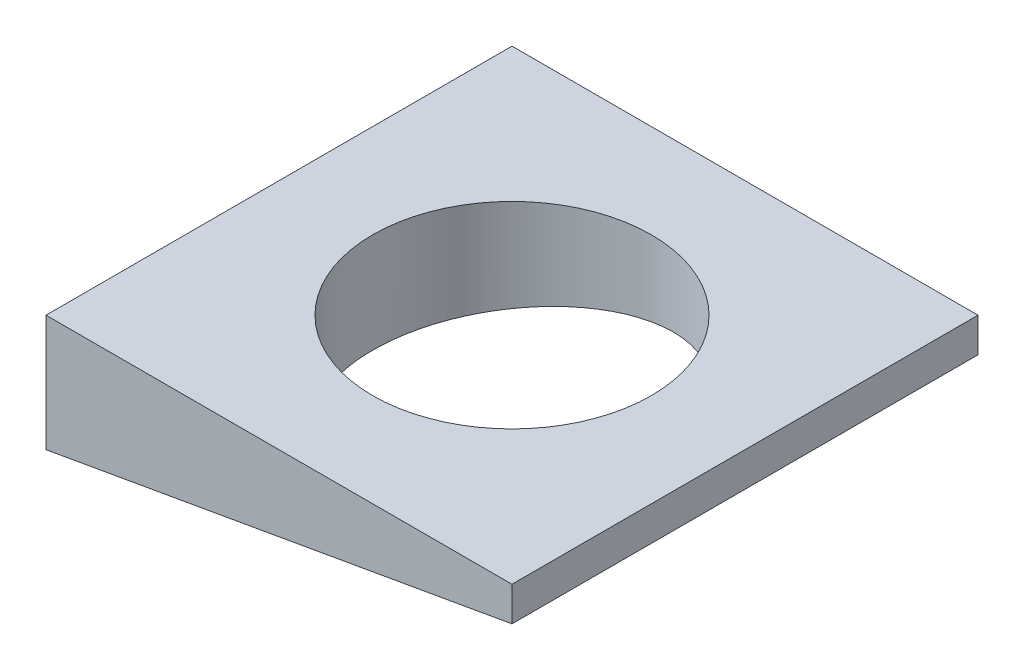
SolidWorks part; units mm, degrees
material "6061 Alloy"
ref_plane "Front Plane" through (0, 0, 0) normal (0, 0, 1) x (1, 0, 0)
ref_plane "Top Plane" through (0, 0, 0) normal (0, 1, 0) x (1, 0, 0)
ref_plane "Right Plane" through (0, 0, 0) normal (1, 0, 0) x (0, 0, -1)
sketch "Sketch1" plane through (0, 0, 0) normal (0, 1, 0) x (1, 0, 0)
  line L1 (-3.175, -3.175) -> (3.175, -3.175)
  line L2 (-3.175, -3.175) -> (-3.175, 3.175)
  line L3 (-3.175, 3.175) -> (3.175, 3.175)
  line L4 (3.175, -3.175) -> (3.175, 3.175)
  line L5 (-3.175, -3.175) -> (3.175, 3.175) construction
  line L6 (-3.175, 3.175) -> (3.175, -3.175) construction
  point P0 (0, 0)
  dimension "D1" = 6.35
  dimension "D2" = 6.35
extrude "Boss-Extrude1" add sketch "Sketch1" along normal blind 1.5875
sketch "Sketch2" plane through (0, 0, 3.175) normal (0, 0, 1) x (1, 0, 0)
  line L0 (-3.175, 0) -> (3.175, 1.1197)
  line L1 (-3.175, 0) -> (3.175, 0) construction
  line L2 (3.175, 1.5875) -> (3.175, 0) construction
  line L3 (3.175, 1.1197) -> (3.175, 0)
  line L4 (3.175, 0) -> (-3.175, 0)
  dimension "D1" = 0
  dimension "D2" = 80
extrude "Cut-Extrude1" cut sketch "Sketch2" against normal through all
hole_wizard "#6 Clearance Hole1" positions "Sketch3" profile "Sketch4" hole size "#6" standard "ANSI Inch" end condition through all
sketch "Sketch3" plane through (0, 1.5875, 0) normal (0, 1, 0) x (1, 0, 0)
  point P0 (0, 0)
sketch "Sketch4" plane through (0, 1.5875, 0) normal (1, 0, 0) x (0, 0, 1)
  line L0 (0, 0) -> (0, 1.5875)
  line L1 (0, 1.5875) -> (1.8986, 1.5875)
  line L2 (1.8986, 1.5875) -> (1.8986, 0)
  line L5 (1.8986, 0) -> (0, 0)
  line L11 (0, -6.35) -> (0, 107.95) construction
  dimension "Thru Hole Dia." = 3.7973
  dimension "Thru Hole Depth" = 1.5875
